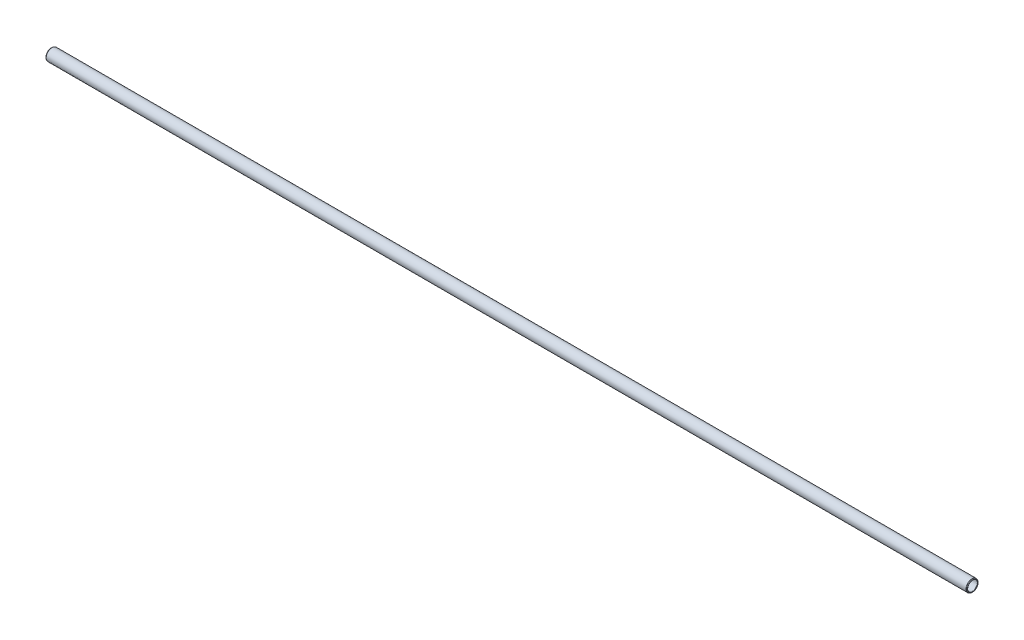
SolidWorks part; units mm, degrees
material "AISI 304"
ref_plane "Front Plane" through (0, 0, 0) normal (0, 0, 1) x (1, 0, 0)
ref_plane "Top Plane" through (0, 0, 0) normal (0, 1, 0) x (1, 0, 0)
ref_plane "Right Plane" through (0, 0, 0) normal (1, 0, 0) x (0, 0, -1)
ref_plane "Plane1" through (959.358, 0, 0) normal (1, 0, 0) x (0, 0, -1)
sketch "Sketch1" plane through (0, 0, 0) normal (0, 0, 1) x (1, 0, 0)
  line L0 (-0.3964, 5.305) -> (-0.254, 5.1626)
  line L1 (-0.254, 5.1626) -> (0, 5.1626)
  line L2 (0, 5.1626) -> (0.508, 5.6706)
  line L3 (0.508, 5.6706) -> (958.85, 5.6706)
  line L4 (958.85, 5.6706) -> (959.358, 5.1626)
  line L5 (959.358, 5.1626) -> (959.612, 5.1626)
  line L6 (959.612, 5.1626) -> (959.7544, 5.305)
  line L7 (959.7544, 5.4846) -> (959.2219, 6.0171)
  line L8 (958.8627, 6.1658) -> (0.4953, 6.1658)
  line L9 (0.1361, 6.0171) -> (-0.3964, 5.4846)
  line L10 (959.358, 0) -> (0, 0) construction
  arc A0 (-0.3964, 5.4846) -> (-0.3964, 5.305) centre (-0.3066, 5.3948) ccw
  arc A1 (959.7544, 5.305) -> (959.7544, 5.4846) centre (959.6646, 5.3948) ccw
  arc A2 (959.2219, 6.0171) -> (958.8627, 6.1658) centre (958.8627, 5.6579) ccw
  arc A3 (0.4953, 6.1658) -> (0.1361, 6.0171) centre (0.4953, 5.6578) ccw
revolve "Revolve1" add sketch "Sketch1" angle 360 about L10 reverse direction yes
ref_plane "Plane2" through (479.679, 0, 0) normal (1, 0, 0) x (0, 0, -1)
ref_plane "cp1 XY" through (479.679, 0, 0) normal (1, 0, 0) x (0, 0, -1)
ref_plane "cp1 XZ" through (0, 6.1658, 0) normal (0, -1, 0) x (-1, 0, 0)
ref_plane "cp1 YZ" through (0, 0, 0) normal (0, 0, -1) x (-1, 0, 0)
ref_axis "cp1 X" through (479.679, 6.1658, 80.9) along (0, 0, -1)
ref_axis "cp1 Y" through (479.679, -50, 0) along (0, 1, 0)
ref_axis "cp1 Z" through (80.9, 6.1658, 0) along (-1, 0, 0)
sketch3d "cp1"
  point P0 (479.679, 6.1658, 0)
ref_plane "cp2 XY" through (479.679, 0, 0) normal (1, 0, 0) x (0, 0, -1)
ref_plane "cp2 XZ" through (0, 0, 0) normal (0, -1, 0) x (-1, 0, 0)
ref_plane "cp2 YZ" through (0, 0, -6.1658) normal (0, 0, -1) x (-1, 0, 0)
ref_axis "cp2 X" through (479.679, 0, 80.9) along (0, 0, -1)
ref_axis "cp2 Y" through (479.679, -50, -6.1658) along (0, 1, 0)
ref_axis "cp2 Z" through (80.9, 0, -6.1658) along (-1, 0, 0)
sketch3d "cp2"
  point P0 (479.679, 0, -6.1658)
ref_plane "cp3 XY" through (479.679, 0, 0) normal (1, 0, 0) x (0, 0, -1)
ref_plane "cp3 XZ" through (0, -6.1658, 0) normal (0, -1, 0) x (-1, 0, 0)
ref_plane "cp3 YZ" through (0, 0, 0) normal (0, 0, -1) x (-1, 0, 0)
ref_axis "cp3 X" through (479.679, -6.1658, 80.9) along (0, 0, -1)
ref_axis "cp3 Y" through (479.679, -50, 0) along (0, 1, 0)
ref_axis "cp3 Z" through (80.9, -6.1658, 0) along (-1, 0, 0)
sketch3d "cp3"
  point P0 (479.679, -6.1658, 0)
ref_plane "cp4 XY" through (479.679, 0, 0) normal (1, 0, 0) x (0, 0, -1)
ref_plane "cp4 XZ" through (0, 0, 0) normal (0, -1, 0) x (-1, 0, 0)
ref_plane "cp4 YZ" through (0, 0, 6.1658) normal (0, 0, -1) x (-1, 0, 0)
ref_axis "cp4 X" through (479.679, 0, 80.9) along (0, 0, -1)
ref_axis "cp4 Y" through (479.679, -50, 6.1658) along (0, 1, 0)
ref_axis "cp4 Z" through (80.9, 0, 6.1658) along (-1, 0, 0)
sketch3d "cp4"
  point P0 (479.679, 0, 6.1658)
ref_plane "tube_front XY" through (0, 0, 0) normal (1, 0, 0) x (0, 0, -1)
ref_plane "tube_front XZ" through (0, 0, 0) normal (0, -1, 0) x (-1, 0, 0)
ref_plane "tube_front YZ" through (0, 0, 0) normal (0, 0, -1) x (-1, 0, 0)
ref_axis "tube_front X" through (0, 0, 80.9) along (0, 0, -1)
ref_axis "tube_front Y" through (0, -50, 0) along (0, 1, 0)
ref_axis "tube_front Z" through (80.9, 0, 0) along (-1, 0, 0)
sketch3d "tube_front"
  point P0 (0, 0, 0)
ref_plane "tube_rear XY" through (959.358, 0, 0) normal (1, 0, 0) x (0, 0, -1)
ref_plane "tube_rear XZ" through (0, 0, 0) normal (0, -1, 0) x (-1, 0, 0)
ref_plane "tube_rear YZ" through (0, 0, 0) normal (0, 0, -1) x (-1, 0, 0)
ref_axis "tube_rear X" through (959.358, 0, 80.9) along (0, 0, -1)
ref_axis "tube_rear Y" through (959.358, -50, 0) along (0, 1, 0)
ref_axis "tube_rear Z" through (80.9, 0, 0) along (-1, 0, 0)
sketch3d "tube_rear"
  point P0 (959.358, 0, 0)
